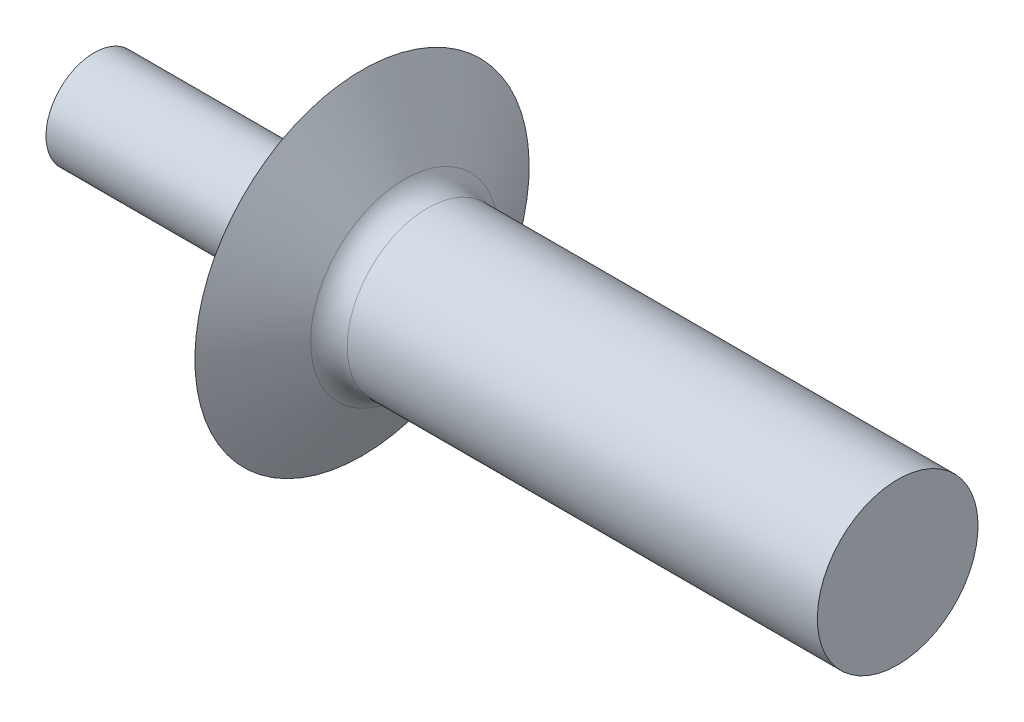
SolidWorks part; units mm, degrees
ref_plane "Front" through (0, 0, 0) normal (0, 0, 1) x (1, 0, 0)
ref_plane "Top" through (0, 0, 0) normal (0, 1, 0) x (1, 0, 0)
ref_plane "Right" through (0, 0, 0) normal (1, 0, 0) x (0, 0, -1)
sketch "Sketch1" plane through (23.9153, 20.7953, 0) normal (0, 0, 1) x (0, 1, 0)
  line L0 (-20.7953, 8.9153) -> (-19.2953, 8.9153)
  line L1 (-19.2953, 8.9153) -> (-19.2953, 17.98)
  line L2 (-19.2953, 17.98) -> (-17.6753, 18.9153)
  line L3 (-17.6753, 18.9153) -> (-19.8953, 18.9153)
  line L4 (-19.8953, 18.9153) -> (-19.8953, 23.9153)
  line L5 (-20.7953, 51.1695) -> (-20.7953, -6.4589) construction
  line L6 (-19.8953, 23.9153) -> (-20.7953, 23.9153)
  line L7 (-20.7953, 23.9153) -> (-20.7953, 8.9153)
  dimension "D5" = 60
revolve "Base-Revolve" add sketch "Sketch1" angle 360 about L5
fillet "Fillet1" radius 0.5 1 edges at (5.9353, -1.5, 0)
equation "\"l1@Sketch1\" = \"l@Sketch1\" / 2"
